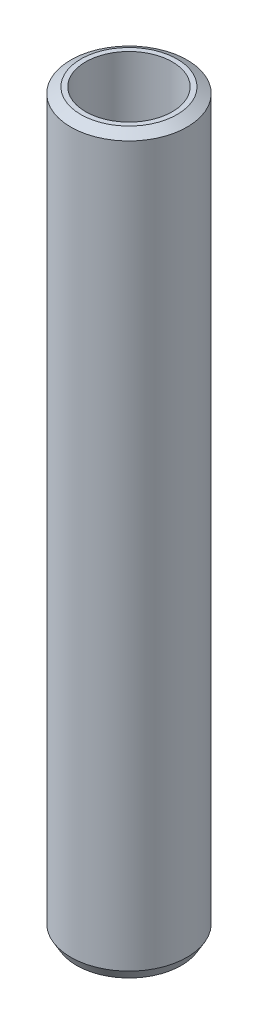
SolidWorks part; units mm, degrees
ref_plane "Front Plane" through (0, 0, 0) normal (0, 0, 1) x (1, 0, 0)
ref_plane "Top Plane" through (0, 0, 0) normal (0, 1, 0) x (1, 0, 0)
ref_plane "Right Plane" through (0, 0, 0) normal (1, 0, 0) x (0, 0, -1)
sketch "Sketch1" plane through (0, 0, 0) normal (0, 1, 0) x (1, 0, 0)
  circle A0 centre (0, 0) radius 47.5
  dimension "SHAFT_OD" = 95
extrude "Boss-Extrude1" add sketch "Sketch1" along normal blind 600
sketch "Sketch2" plane through (0, 0, 0) normal (0, 1, 0) x (1, 0, 0)
  circle A0 centre (0, 0) radius 35.3493
  dimension "BORE_D" = 70.6986
extrude "Cut-Extrude1" cut sketch "Sketch2" along normal through all
chamfer "Chamfer1" distance 4.7351 angle 60 2 edges at (0, 600, 47.5) (0, 0, 47.5) first distance on face at (0, 600, 47.5) first distance on face at (0, 0, 35.3493)
